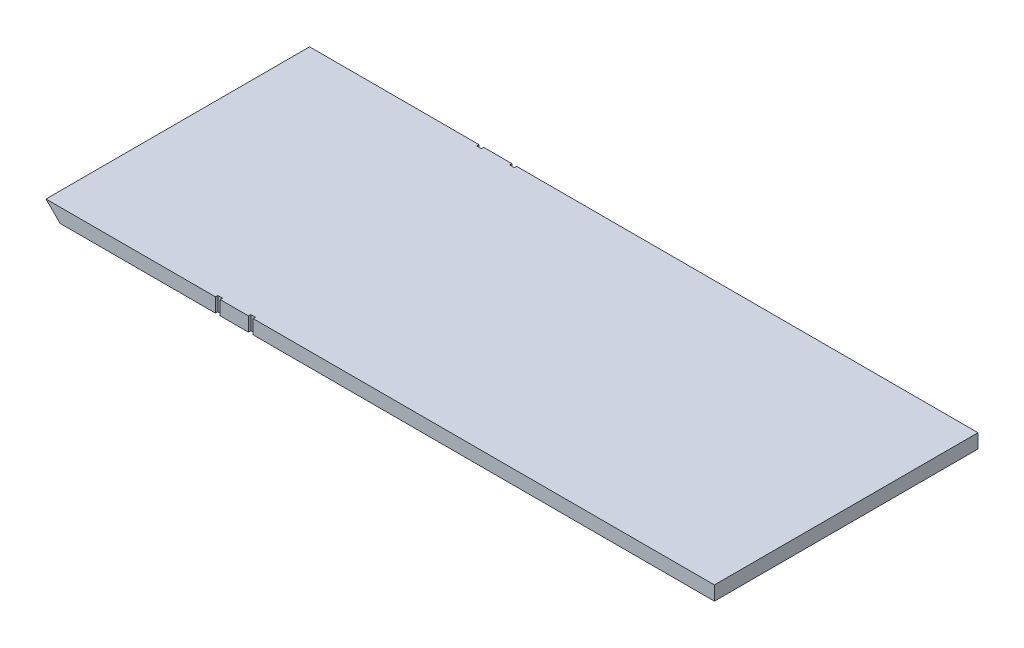
SolidWorks part; units mm, degrees
ref_plane "Front Plane" through (0, 0, 0) normal (0, 0, 1) x (1, 0, 0)
ref_plane "Top Plane" through (0, 0, 0) normal (0, 1, 0) x (1, 0, 0)
ref_plane "Right Plane" through (0, 0, 0) normal (1, 0, 0) x (0, 0, -1)
sketch "Sketch1" plane through (0, 0, 0) normal (0, 1, 0) x (1, 0, 0)
  line L1 (-450.85, 177.8) -> (450.85, 177.8)
  line L2 (-450.85, 177.8) -> (-450.85, -177.8)
  line L3 (-450.85, -177.8) -> (450.85, -177.8)
  line L4 (450.85, 177.8) -> (450.85, -177.8)
  line L5 (-450.85, 177.8) -> (450.85, -177.8) construction
  line L6 (-450.85, -177.8) -> (450.85, 177.8) construction
  point P0 (0, 0)
  dimension "D1" = 355.6
  dimension "D2" = 901.7
extrude "Boss-Extrude1" add sketch "Sketch1" along normal mid plane 19.05
chamfer "Chamfer1" distance 19.05 angle 45 1 edges at (-450.85, -9.525, 0)
sketch "Sketch2" plane through (0, 0, 177.8) normal (0, 0, 1) x (1, 0, 0)
  line L0 (-171.45, -142.875) -> (-171.45, 9.525) construction
  line L1 (-177.8, 9.525) -> (-171.45, 9.525) construction
  line L2 (-177.8, -142.875) -> (-177.8, 9.525) construction
  line L3 (-222.25, 9.525) -> (-215.9, 9.525) construction
  line L4 (-215.9, 9.525) -> (-215.9, -142.875) construction
  line L5 (-222.25, 9.525) -> (-222.25, -142.875) construction
  line L6 (-171.45, -9.525) -> (-171.45, 9.525)
  line L7 (-177.8, 9.525) -> (-171.45, 9.525)
  line L8 (-177.8, -9.525) -> (-177.8, 9.525)
  line L9 (-222.25, 9.525) -> (-215.9, 9.525)
  line L10 (-215.9, 9.525) -> (-215.9, -9.525)
  line L11 (-222.25, 9.525) -> (-222.25, -9.525)
  line L12 (-177.8, -9.525) -> (-171.45, -9.525)
  line L13 (-431.8, -9.525) -> (450.85, -9.525) construction
  line L14 (-222.25, -9.525) -> (-215.9, -9.525)
extrude "Cut-Extrude1" cut sketch "Sketch2" against normal blind 3.175
sketch "Sketch3" plane through (0, 0, -177.8) normal (0, 0, -1) x (-1, 0, 0)
  line L0 (177.8, 9.525) -> (171.45, 9.525) construction
  line L1 (222.25, 9.525) -> (215.9, 9.525) construction
  line L2 (171.45, 9.525) -> (171.45, -142.875) construction
  line L3 (177.8, 9.525) -> (177.8, -142.875) construction
  line L4 (215.9, -142.875) -> (215.9, 9.525) construction
  line L5 (222.25, -142.875) -> (222.25, 9.525) construction
  line L6 (177.8, 9.525) -> (171.45, 9.525)
  line L7 (222.25, 9.525) -> (215.9, 9.525)
  line L8 (171.45, 9.525) -> (171.45, -9.525)
  line L9 (177.8, 9.525) -> (177.8, -9.525)
  line L10 (215.9, -9.525) -> (215.9, 9.525)
  line L11 (222.25, -9.525) -> (222.25, 9.525)
  line L12 (222.25, -9.525) -> (215.9, -9.525)
  line L13 (-450.85, -9.525) -> (431.8, -9.525) construction
  line L14 (177.8, -9.525) -> (171.45, -9.525)
extrude "Cut-Extrude2" cut sketch "Sketch3" against normal blind 3.175
